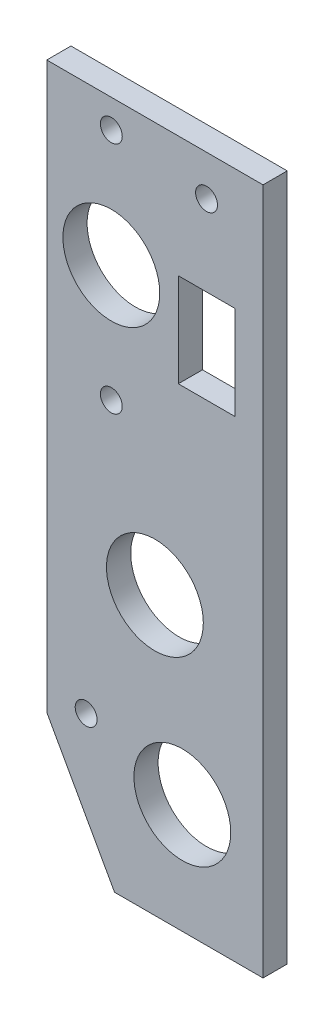
SolidWorks part; units mm, degrees
material "Acrylic (Medium-high impact)"
ref_plane "Front Plane" through (0, 0, 0) normal (0, 0, 1) x (1, 0, 0)
ref_plane "Top Plane" through (0, 0, 0) normal (0, 1, 0) x (1, 0, 0)
ref_plane "Right Plane" through (0, 0, 0) normal (1, 0, 0) x (0, 0, -1)
sketch "Sketch1" plane through (0, 0, 0) normal (0, 0, 1) x (1, 0, 0)
  line L5 (-44.1325, -84.1375) -> (-30.7975, -108.1405)
  line L6 (-30.7975, -108.1405) -> (-1.5875, -108.1405)
  line L7 (-1.5875, -108.1405) -> (-1.5875, 26.9875)
  line L8 (-1.5875, 26.9875) -> (-44.1325, 26.9875)
  line L9 (-44.1325, 26.9875) -> (-44.1325, -84.1375)
  line L10 (-44.1325, -84.1375) -> (-30.7975, -108.1405)
  line L11 (-30.7975, -108.1405) -> (-1.5875, -108.1405)
  line L12 (-1.5875, -108.1405) -> (-1.5875, 26.9875)
  line L13 (-1.5875, 26.9875) -> (-44.1325, 26.9875)
  line L14 (-44.1325, 26.9875) -> (-44.1325, -84.1375)
  dimension "D1" = 0
extrude "Boss-Extrude1" add sketch "Sketch1" along normal blind 4.7625
hole_wizard "3/4 (0.75) Diameter Hole1" positions "Sketch3" profile "Sketch2" hole size "3/4" standard "ANSI Inch" end condition through all
sketch "Sketch3" plane through (0, 0, 4.7625) normal (0, 0, 1) x (1, 0, 0)
  point P0 (-31.4325, -1.6203)
  point P3 (-17.4625, -86.5505)
  point P7 (-22.86, -53.5305)
sketch "Sketch2" plane through (-31.4325, -1.6203, 4.7625) normal (1, 0, 0) x (0, -1, 0)
  line L0 (0, 0) -> (0, 4.7625)
  line L1 (0, 4.7625) -> (9.525, 4.7625)
  line L2 (9.525, 4.7625) -> (9.525, 0)
  line L5 (9.525, 0) -> (0, 0)
  line L11 (0, -6.35) -> (0, 107.95) construction
  dimension "Thru Hole Dia." = 19.05
  dimension "Thru Hole Depth" = 4.7625
sketch "Sketch4" plane through (0, 0, 4.7625) normal (0, 0, 1) x (1, 0, 0)
  line L0 (-12.7, 11.5609) -> (-12.7, -34.5498) construction
  line L1 (-18.2563, 3.175) -> (-7.1438, 3.175)
  line L2 (-18.2563, 3.175) -> (-18.2563, -15.24)
  line L3 (-18.2563, -15.24) -> (-7.1438, -15.24)
  line L4 (-7.1438, 3.175) -> (-7.1438, -15.24)
  line L5 (-18.2563, 3.175) -> (-7.1438, -15.24) construction
  line L6 (-18.2563, -15.24) -> (-7.1438, 3.175) construction
  point P4 (-12.7, -6.0325)
  point P8 (-12.7, 19.05)
  dimension "D1" = 11.1125
  dimension "D2" = 18.415
  dimension "D3" = 15.875
extrude "Cut-Extrude1" cut sketch "Sketch4" against normal through all
hole_wizard "#6 Clearance Hole1" positions "Sketch6" profile "Sketch5" hole size "#6" standard "ANSI Inch" end condition through all
sketch "Sketch6" plane through (0, 0, 4.7625) normal (0, 0, 1) x (1, 0, 0)
  point P0 (-36.3855, -80.4545)
  point P3 (-12.7, 19.05)
  point P6 (-31.4325, 21.4048)
  point P9 (-31.4325, -24.62)
sketch "Sketch5" plane through (-36.3855, -80.4545, 4.7625) normal (1, 0, 0) x (0, -1, 0)
  line L0 (0, 0) -> (0, 4.7625)
  line L1 (0, 4.7625) -> (2.1526, 4.7625)
  line L2 (2.1526, 4.7625) -> (2.1526, 0)
  line L5 (2.1526, 0) -> (0, 0)
  line L11 (0, -6.35) -> (0, 107.95) construction
  dimension "Thru Hole Dia." = 4.3053
  dimension "Thru Hole Depth" = 4.7625
